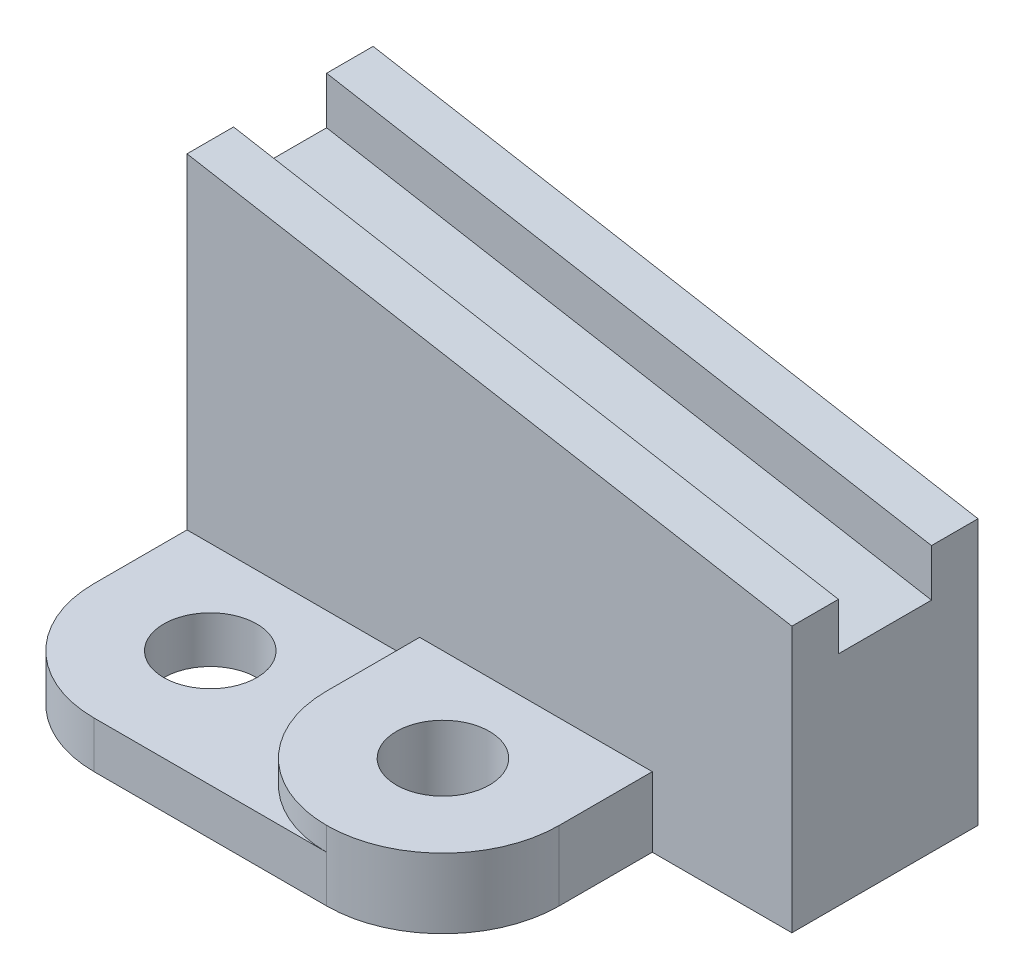
SolidWorks part; units mm, degrees
ref_plane "Plano frontal" through (0, 0, 0) normal (0, 0, 1) x (1, 0, 0)
ref_plane "Plano superior" through (0, 0, 0) normal (0, 1, 0) x (1, 0, 0)
ref_plane "Plano direito" through (0, 0, 0) normal (1, 0, 0) x (0, 0, -1)
sketch "Esboço1" plane through (0, 0, 0) normal (0, 0, 1) x (1, 0, 0)
  line L0 (-53.2953, 9.3008) -> (76.7047, 9.3008)
  line L1 (-53.2953, 9.3008) -> (-53.2953, 89.3008)
  line L2 (76.7047, 9.3008) -> (76.7047, 66.3783)
  line L3 (-53.2953, 89.3008) -> (76.7047, 66.3783)
  dimension "D1" = 100
  dimension "D2" = 80
  dimension "D3" = 130
extrude "Ressalto-extrusão1" add sketch "Esboço1" along normal blind 40
sketch "Esboço3" [suppressed] plane through (13.6643, 77.494, 0) normal (0.1736, 0.9848, 0) x (0.9848, -0.1736, 0)
  line L0 (64.0129, -40) -> (-67.9926, -40) construction
  line L1 (-71.0201, -30) -> (70.4962, -30)
  line L2 (-71.0201, -30) -> (-71.0201, -10)
  line L3 (-71.0201, -10) -> (70.4962, -10)
  line L4 (70.4962, -30) -> (70.4962, -10)
  line L5 (64.0129, 0) -> (-67.9926, 0) construction
  dimension "D1" = 10
  dimension "D2" = 10
extrude "Corte-extrusão2" [suppressed] cut sketch "Esboço3" against normal blind 10
sketch "Esboço4" plane through (13.6643, 77.494, 0) normal (0.1736, 0.9848, 0) x (0.9848, -0.1736, 0)
  line L0 (64.0129, 0) -> (-67.9926, 0) construction
  line L1 (-77.3839, -10) -> (94.2466, -10)
  line L2 (-77.3839, -10) -> (-77.3839, -30)
  line L3 (-77.3839, -30) -> (94.2466, -30)
  line L4 (94.2466, -10) -> (94.2466, -30)
  line L5 (64.0129, -40) -> (-67.9926, -40) construction
  dimension "D1" = 10
  dimension "D2" = 10
extrude "Corte-extrusão3" cut sketch "Esboço4" against normal blind 10
sketch "Esboço5" plane through (0, 0, 40) normal (0, 0, 1) x (1, 0, 0)
  line L1 (-53.2953, 9.3008) -> (46.7047, 9.3008)
  line L2 (-53.2953, 9.3008) -> (-53.2953, 24.3008)
  line L3 (-53.2953, 24.3008) -> (46.7047, 24.3008)
  line L4 (46.7047, 9.3008) -> (46.7047, 24.3008)
  line L5 (-53.2953, 9.3008) -> (-3.2953, 9.3008)
  line L6 (-53.2953, 9.3008) -> (-53.2953, 24.3008)
  line L7 (-53.2953, 24.3008) -> (-3.2953, 24.3008)
  line L8 (-3.2953, 9.3008) -> (-3.2953, 24.3008)
  dimension "D1" = 15
  dimension "D2" = 100
extrude "Ressalto-extrusão2" add sketch "Esboço5" along normal blind 45 contours L3 L4 L1 L2
extrude "Corte-extrusão6" cut sketch "Esboço6" against normal through all
sketch "Esboço6" plane through (0, 24.3008, 0) normal (0, 1, 0) x (1, 0, 0)
  line L0 (-53.2953, -40) -> (46.7047, -40) construction
  line L1 (-28.2953, -85) -> (21.7047, -85) construction
  line L2 (-53.2953, -60) -> (-53.2953, -40) construction
  circle A0 centre (-28.2953, -60) radius 10
  circle A1 centre (21.7047, -60) radius 10
  dimension "D1" = 50
  dimension "D3" = 25
  dimension "D4" = 25
  dimension "D5" = 20
  dimension "D6" = 25
  dimension "D2" = 20
fillet "Filete8" radius 25 1 edges at (46.7047, 16.8008, 85)
fillet "Filete7" radius 25 1 edges at (-53.2953, 16.8008, 85)
sketch "Esboço9" plane through (0, 24.3008, 0) normal (0, 1, 0) x (1, 0, 0)
  line L0 (-53.2953, -40) -> (-3.2953, -40) construction
  line L1 (-53.2953, -40) -> (-3.2953, -40)
  line L2 (-53.2953, -40) -> (-53.2953, -85)
  line L3 (-53.2953, -85) -> (-3.2953, -85)
  line L4 (-3.2953, -40) -> (-3.2953, -85)
  line L5 (-53.2953, -60) -> (-53.2953, -40) construction
  line L6 (-28.2953, -85) -> (21.7047, -85) construction
extrude "Corte-extrusão7" cut sketch "Esboço9" against normal blind 5
fillet "Filete9" radius 25 1 edges at (-3.2953, 21.8008, 85)
sketch "Esboço10" plane through (0, 19.3008, 0) normal (0, 1, 0) x (1, 0, 0)
